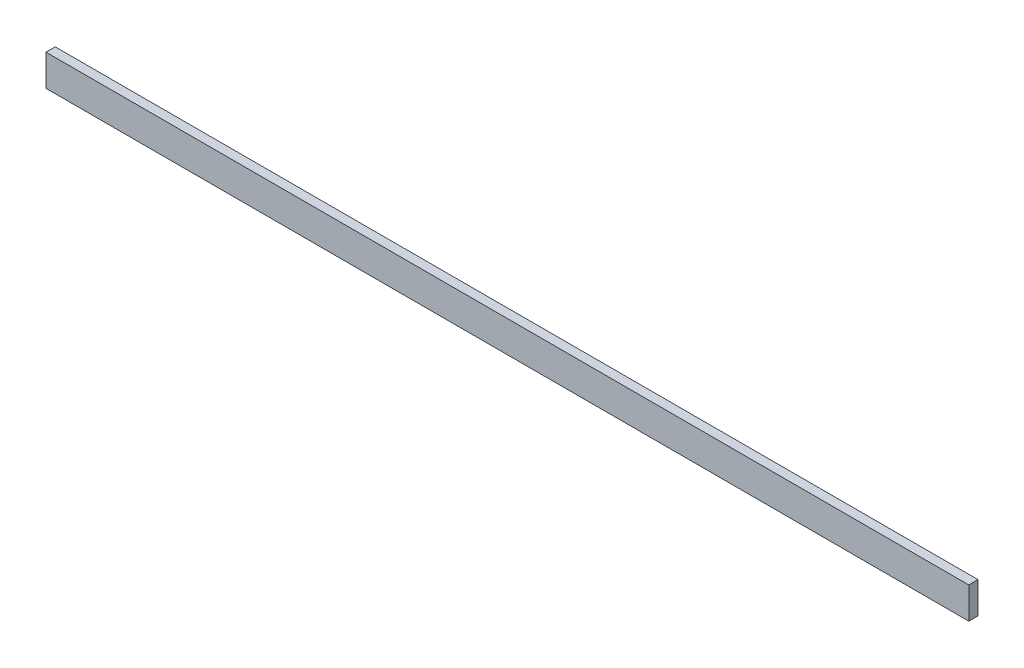
SolidWorks part; units mm, degrees
material "Oak"
ref_plane "Front Plane" through (0, 0, 0) normal (0, 0, 1) x (1, 0, 0)
ref_plane "Top Plane" through (0, 0, 0) normal (0, 1, 0) x (1, 0, 0)
ref_plane "Right Plane" through (0, 0, 0) normal (1, 0, 0) x (0, 0, -1)
sketch "Sketch1" plane through (0, 0, 0) normal (0, 0, 1) x (1, 0, 0)
  line L1 (-250, 8.5) -> (250, 8.5)
  line L2 (-250, 8.5) -> (-250, -8.5)
  line L3 (-250, -8.5) -> (250, -8.5)
  line L4 (250, 8.5) -> (250, -8.5)
  line L5 (-250, 8.5) -> (250, -8.5) construction
  line L6 (-250, -8.5) -> (250, 8.5) construction
  point P0 (0, 0)
  dimension "D1" = 500
  dimension "D2" = 17
base flange "Base-Flange1" sketch "Sketch1" thickness 5 reverse thickness direction no parameters "D1"=0.7366
sketch "Bend-Lines1" [suppressed] plane through (0, 0, 0) normal (0, 1, 0) x (1, 0, 0)
sketch "Bounding-Box1" [suppressed] plane through (0, 0, 0) normal (0, 1, 0) x (1, 0, 0)
sheet metal parameters "Sheet-Metal1" thickness 5 parameters "D1"=0.7366
flat pattern "Flat-Pattern1" [suppressed]
sketch "Bend-Lines2" plane through (0, 0, 0) normal (0, 1, 0) x (1, 0, 0)
sketch3d "Bounding-Box2" [suppressed]
  line L0 (250, -8.5, 0) -> (-250, -8.5, 0) construction
  line L1 (250, 8.5, 0) -> (-250, 8.5, 0) construction
  line L2 (250, -8.5, 0) -> (250, 8.5, 0) construction
  line L3 (-250, -8.5, 0) -> (-250, 8.5, 0) construction
